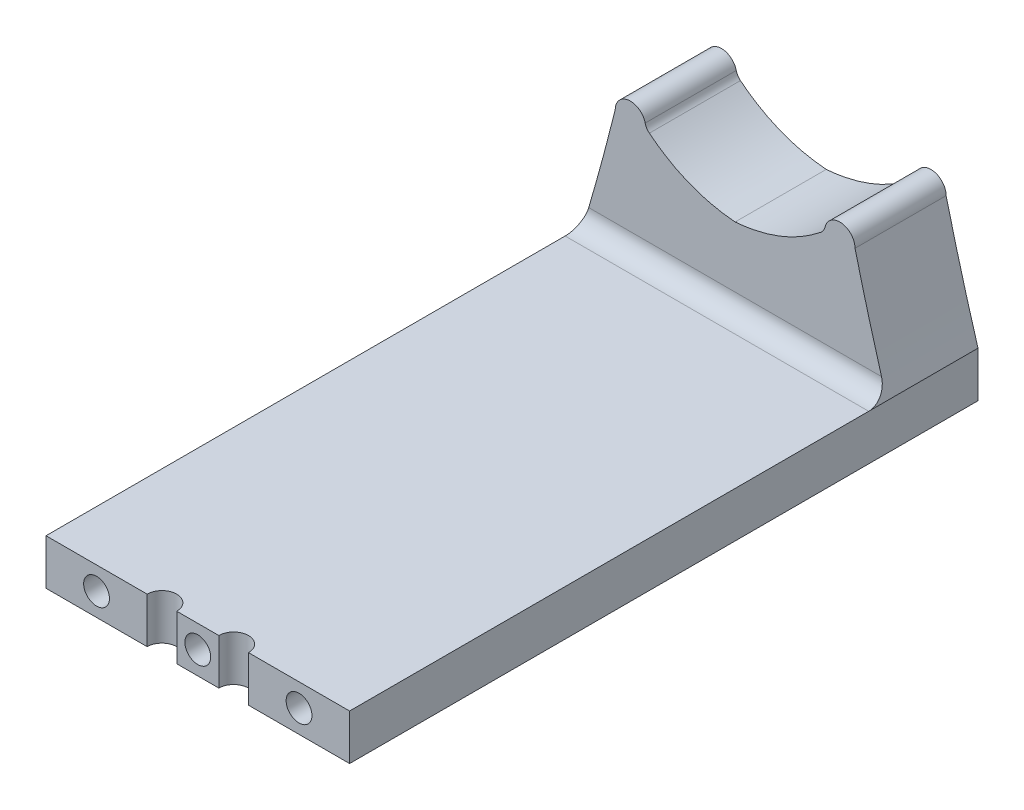
SolidWorks part; units mm, degrees
ref_plane "Front Plane" through (0, 0, 0) normal (0, 0, 1) x (1, 0, 0)
ref_plane "Top Plane" through (0, 0, 0) normal (0, 1, 0) x (1, 0, 0)
ref_plane "Right Plane" through (0, 0, 0) normal (1, 0, 0) x (0, 0, -1)
sketch "Sketch1" plane through (0, 0, 0) normal (0, 0, 1) x (1, 0, 0)
  line L0 (-996.8903, -40.64) -> (49003.1097, -40.64) construction
  line L1 (0, -1000) -> (0, 49000) construction
  line L2 (0, 0) -> (-23.4635, -40.64) construction
  line L3 (0, 0) -> (-40.64, -40.64) construction
  line L4 (-31.75, -62.23) -> (-31.75, -71.755)
  line L5 (-31.75, -71.755) -> (31.75, -71.755)
  line L6 (31.75, -62.23) -> (31.75, -71.755)
  line L7 (-957.5735, -46.99) -> (49042.4265, -46.99) construction
  circle A0 centre (0, 0) radius 40.64 construction
  arc A1 (-18.7325, -37.9449) -> (-25.0825, -37.9449) centre (-21.9075, -37.9449) ccw
  arc A2 (18.7325, -37.9449) -> (25.0825, -37.9449) centre (21.9075, -37.9449) cw
  spline S0 degree 2 poles (-18.7325, -37.9449) (-10.6333, -44.8669) (0, -45.72) knots 0 0 0 1 1 1
  spline S1 degree 2 poles (-25.0825, -37.9449) (-28.1202, -50.167) (-31.75, -62.23) knots 0 0 0 1 1 1
  spline S2 degree 2 poles (25.0825, -37.9449) (28.1202, -50.167) (31.75, -62.23) knots 0 0 0 1 1 1
  spline S3 degree 2 poles (18.7325, -37.9449) (10.6333, -44.8669) (0, -45.72) knots 0 0 0 1 1 1
  point P13 (0, -71.755)
  dimension "D1" = 81.28
  dimension "D3" = 6.35
  dimension "D5" = 5.08
  dimension "D2" = 30
  dimension "D4" = 45
  dimension "D6" = 31.75
  dimension "D7" = 9.525
  dimension "D8" = 21.59
  dimension "D9" = 6.35
extrude "Boss-Extrude1" add sketch "Sketch1" along normal mid plane 19.05
sketch "Sketch2" plane through (0, 0, 0) normal (0, 0, 1) x (1, 0, 0)
  line L1 (-31.75, -62.23) -> (31.75, -62.23)
  line L2 (-31.75, -62.23) -> (-31.75, -71.755)
  line L3 (-31.75, -71.755) -> (31.75, -71.755)
  line L4 (31.75, -62.23) -> (31.75, -71.755)
extrude "Boss-Extrude2" add sketch "Sketch2" along normal blind 121.92
fillet "Fillet2" radius 2.54 2 edges at (18.7325, -37.9449, 0) (-18.7325, -37.9449, 0)
sketch "Sketch3" plane through (0, -62.23, 0) normal (0, 1, 0) x (1, 0, 0)
  line L0 (31.75, -121.92) -> (-31.75, -121.92) construction
  line L1 (0, -9.525) -> (0, 9.525) construction
  circle A0 centre (7.5, -121.92) radius 3.1
  circle A1 centre (-7.5, -121.92) radius 3.1
  dimension "D1" = 6.2
  dimension "D2" = 7.5
extrude "Cut-Extrude1" cut sketch "Sketch3" against normal through all
ref_plane "wheel_tangent_plane" through (0, -40.64, 0) normal (0, 1, 0) x (1, 0, 0)
ref_plane "offset_0.1in_aka_poly_top" through (0, -43.18, 0) normal (0, 1, 0) x (1, 0, 0)
sketch "Sketch4" plane through (0, 0, 121.92) normal (0, 0, 1) x (1, 0, 0)
  circle A0 centre (-21.175, -66.9925) radius 2.7
  circle A1 centre (0, -66.9925) radius 2.7
  circle A2 centre (21.175, -66.9925) radius 2.7
  dimension "D1" = 5.4
  dimension "D2" = 5.4
  dimension "D3" = 5.4
extrude "Cut-Extrude2" cut sketch "Sketch4" against normal blind 9.525
fillet "Fillet3" radius 3.81 1 edges at (0, -62.23, 9.525) type face fillet first side face at (2.7343, -43.5854, 9.525) second side face at (0, -62.23, 93.0462)
